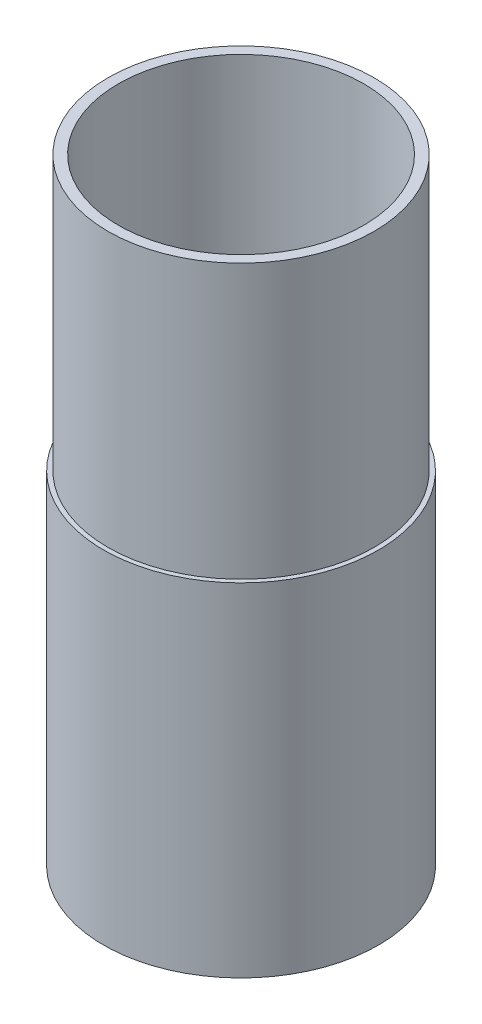
SolidWorks part; units mm, degrees
material "E-Glass Fiber"
ref_plane "Front Plane" through (0, 0, 0) normal (0, 0, 1) x (1, 0, 0)
ref_plane "Top Plane" through (0, 0, 0) normal (0, 1, 0) x (1, 0, 0)
ref_plane "Right Plane" through (0, 0, 0) normal (1, 0, 0) x (0, 0, -1)
sketch "Sketch1" plane through (0, 0, 0) normal (0, 0, 1) x (1, 0, 0)
  line L0 (0, 0) -> (0, 49.7577) construction
  line L1 (22.7624, -56.2737) -> (24.6928, -56.2737)
  line L2 (22.7624, -56.2737) -> (22.7624, 58.0263)
  line L3 (22.7624, 58.0263) -> (24.6928, 58.0263)
  line L4 (24.6928, -56.2737) -> (24.6928, 58.0263)
  line L5 (24.6928, -56.2737) -> (25.5143, -56.2737)
  line L6 (24.6928, -56.2737) -> (24.6928, 7.2263)
  line L7 (24.6928, 7.2263) -> (25.5143, 7.2263)
  line L8 (25.5143, -56.2737) -> (25.5143, 7.2263)
  line L9 (25.5143, -742.0737) -> (25.5143, 7.2263) construction
revolve "Revolve1" add sketch "Sketch1" angle 360 about L0 region at (23.7276, 0.8763, 0) region at (25.1035, -24.5237, 0)
